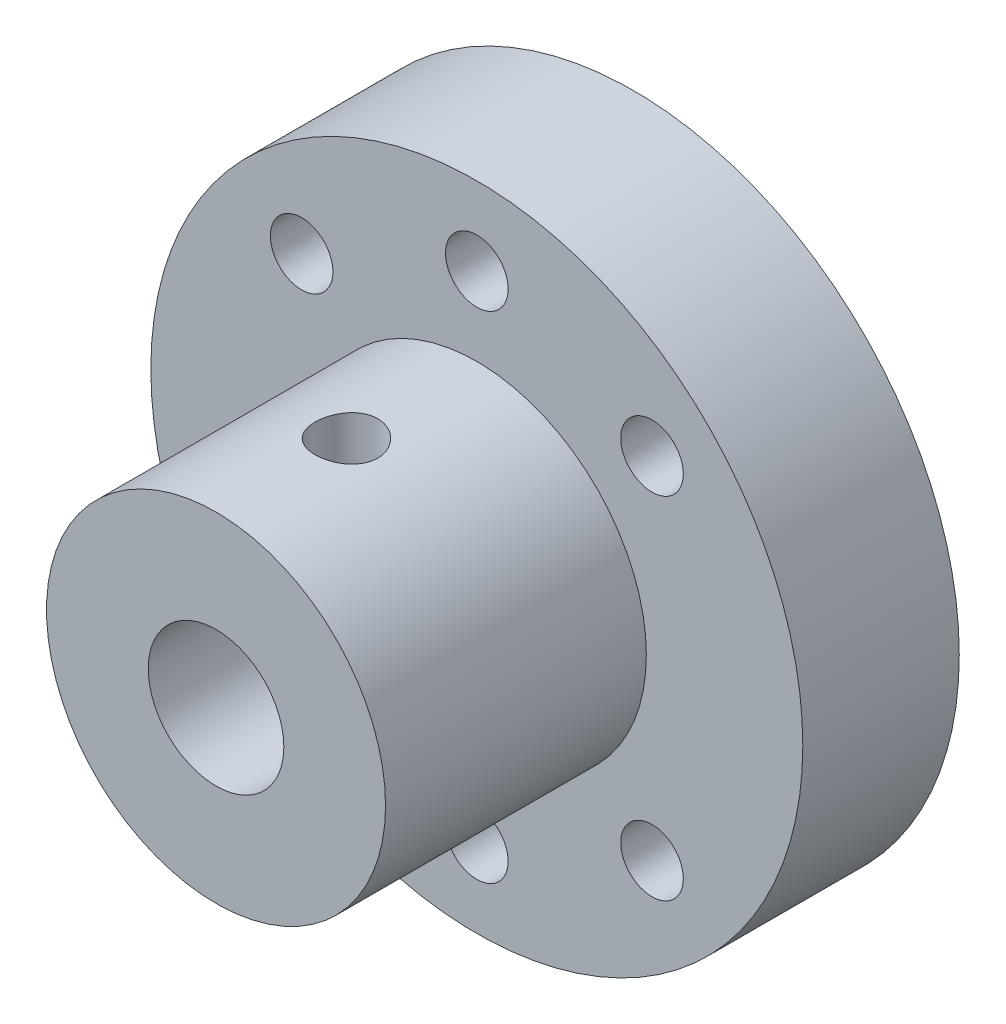
SolidWorks part; units mm, degrees
ref_plane "Front Plane" through (0, 0, 0) normal (0, 0, 1) x (1, 0, 0)
ref_plane "Top Plane" through (0, 0, 0) normal (0, 1, 0) x (1, 0, 0)
ref_plane "Right Plane" through (0, 0, 0) normal (1, 0, 0) x (0, 0, -1)
sketch "Sketch2" plane through (0, 0, 0) normal (0, 0, 1) x (1, 0, 0)
  circle A0 centre (0, 0) radius 12.5
  dimension "D1" = 25
extrude "Boss-Extrude1" add sketch "Sketch2" along normal blind 6
sketch "Sketch3" plane through (0, 0, 6) normal (0, 0, 1) x (1, 0, 0)
  circle A0 centre (0, 0) radius 6.5
  circle A1 centre (0, 0) radius 2.5
  dimension "D1" = 5
  dimension "D2" = 4
extrude "Boss-Extrude2" add sketch "Sketch3" along normal blind 10
sketch "Sketch4" plane through (0, 0, 0) normal (0, 1, 0) x (1, 0, 0)
  line L2 (-12.5, -6) -> (12.5, -6) construction
  circle A0 centre (0, -11) radius 1.2
  dimension "D1" = 2.4
  dimension "D2" = 5
extrude "Cut-Extrude1" cut sketch "Sketch4" against normal blind 25 and the other way blind 25
sketch "Sketch5" plane through (0, 0, 6) normal (0, 0, 1) x (1, 0, 0)
  circle A0 centre (0, 9.5) radius 1.2
  circle A1 centre (0, 0) radius 12.5 construction
  dimension "D1" = 2.4
  dimension "D2" = 9.5
extrude "Cut-Extrude2" cut sketch "Sketch5" against normal blind 25 and the other way blind 25
ref_axis "Axis1" through (0, 0, -0.6) along (0, 0, 1)
pattern_circular "CirPattern1" count 2 every 45 about axis through (0, 0, -0.6) along (0, 0, 1) of "Cut-Extrude2"
sketch "Sketch6" plane through (0, 0, 6) normal (0, 0, 1) x (1, 0, 0)
  circle A0 centre (0, 0) radius 2.6
  dimension "D1" = 5.2
extrude "Cut-Extrude3" cut sketch "Sketch6" against normal blind 20 and the other way blind 50
sketch "Sketch7" plane through (0, 0, 6) normal (0, 0, 1) x (1, 0, 0)
  line L0 (-17.5341, 4.065) -> (20.2194, 4.065) construction
  line L1 (20.2194, 4.065) -> (20.2194, -4.065) construction
  line L2 (20.2194, -4.065) -> (-17.5341, -4.065) construction
  line L3 (-17.5341, -4.065) -> (-17.5341, 4.065) construction
  dimension "D1" = 8.13
  dimension "D2" = 4.065
pattern_circular "CirPattern2" count 2 every 315 about axis through (0, 0, 6) along (0, 0, 1) of "Cut-Extrude2"
mirror "Mirror1" about plane through (0, 0, 0) normal (0, 1, 0) of "CirPattern2", "CirPattern1"
